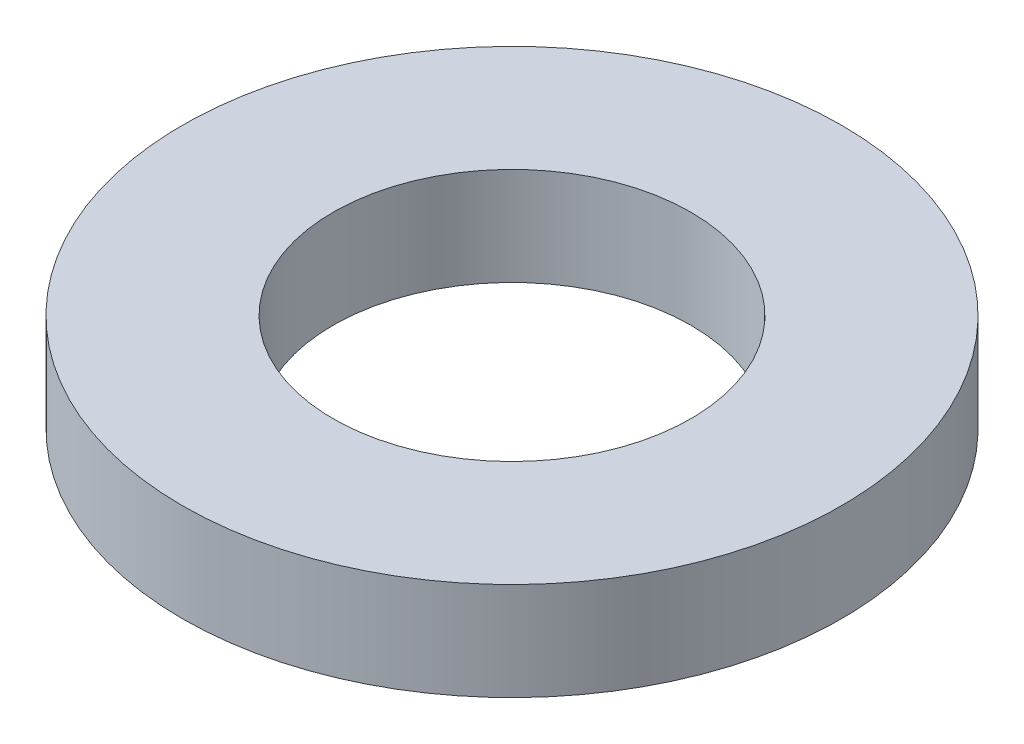
SolidWorks part; units mm, degrees
ref_plane "Front Plane" through (0, 0, 0) normal (0, 0, 1) x (1, 0, 0)
ref_plane "Top Plane" through (0, 0, 0) normal (0, 1, 0) x (1, 0, 0)
ref_plane "Right Plane" through (0, 0, 0) normal (1, 0, 0) x (0, 0, -1)
sketch "Sketch1" plane through (0, 0, 0) normal (0, 1, 0) x (1, 0, 0)
  circle A0 centre (0, 0) radius 87.5
  dimension "FLANGE_OD" = 175
extrude "Boss-Extrude1" add sketch "Sketch1" along normal blind 26
sketch "Sketch2" plane through (0, 0, 0) normal (0, 1, 0) x (1, 0, 0)
  circle A0 centre (0, 0) radius 47.5
  dimension "BORE_D" = 95
extrude "Cut-Extrude1" cut sketch "Sketch2" along normal through all
sketch "Sketch3" plane through (0, 26, 0) normal (0, 1, 0) x (1, 0, 0)
  circle A0 centre (0, 0) radius 39.0551 construction
  circle A1 centre (-39.0551, 0) radius 1.5072
  dimension "BOLT_D" = 3.0145
  dimension "BOLT_PCD" = 78.1103
extrude "Cut-Extrude2" cut sketch "Sketch3" against normal blind 20.9625 rebuild error yes
pattern_circular "CirPattern1" count 6 over 360 rebuild error yes
